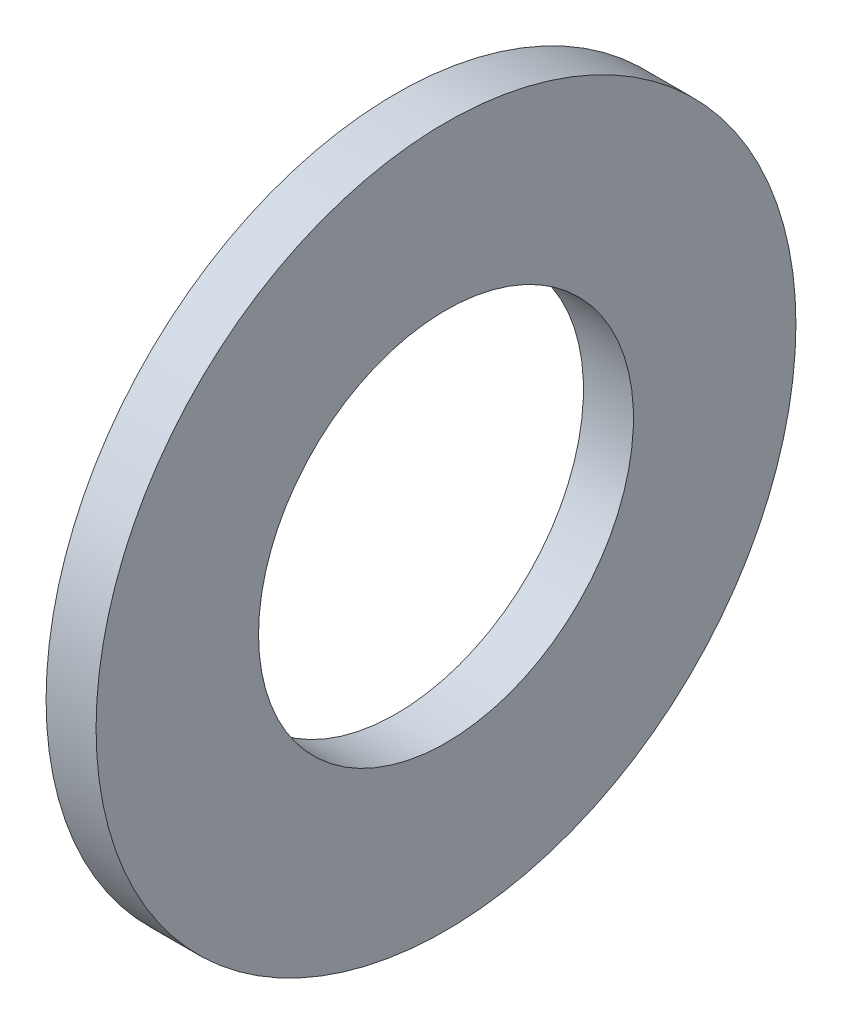
SolidWorks part; units mm, degrees
ref_plane "Front Plane" through (0, 0, 0) normal (0, 0, 1) x (1, 0, 0)
ref_plane "Top Plane" through (0, 0, 0) normal (0, 1, 0) x (1, 0, 0)
ref_plane "Right Plane" through (0, 0, 0) normal (1, 0, 0) x (0, 0, -1)
sketch "Sketch2" plane through (0, 0, 0) normal (0, 0, 1) x (1, 0, 0)
  line L0 (0, 0) -> (58.591, 0) construction
  line L2 (0, 0) -> (18.4, 0)
  line L3 (0, 0) -> (0, 2.5)
  line L4 (0, 2.5) -> (18.4, 2.5)
  line L5 (18.4, 0) -> (18.4, 2.5)
  line L6 (6, 2.5) -> (6, 6)
  line L11 (6, 6) -> (9.97, 6)
  line L16 (12.97, 6) -> (12.97, 3)
  line L17 (12.97, 3) -> (13.6304, 3)
  line L18 (13.6304, 3) -> (13.6304, 2.5)
  line L19 (13.6304, 2.5) -> (6, 2.5)
  line L22 (13.6304, 2.5) -> (16.1104, 2.5)
  line L23 (13.6304, 2.5) -> (13.6304, 4)
  line L24 (13.6304, 4) -> (16.1104, 4)
  line L25 (16.1104, 2.5) -> (16.1104, 4)
  line L27 (6, 6) -> (9.97, 6)
  line L28 (6, 6) -> (6, 9)
  line L29 (6, 9) -> (9.97, 9)
  line L30 (9.97, 6) -> (9.97, 9)
  line L31 (6, 9) -> (6, 8.25)
  line L32 (6, 8.25) -> (5, 8.25)
  line L33 (8.58, 22.001) -> (8.58, 12.476) construction
  line L34 (5, 12.476) -> (12.16, 12.476)
  line L35 (9.97, 9) -> (12.16, 9)
  line L36 (5, 7.5) -> (3, 7.5)
  line L37 (5, 8.25) -> (5, 12.476)
  line L38 (5, 7.5) -> (5, 14)
  line L39 (5, 14) -> (3, 14)
  line L40 (3, 7.5) -> (3, 14)
  line L41 (5, 22.001) -> (12.16, 22.001)
  line L42 (5, 22.001) -> (5, 30.1625)
  line L43 (5, 30.1625) -> (12.16, 30.1625)
  line L44 (12.16, 22.001) -> (12.16, 30.1625)
  line L49 (16.6304, 22.001) -> (16.6304, 7.5)
  line L51 (23.0104, 7.5) -> (23.0104, 6.5)
  line L54 (16.1104, 4) -> (13.6304, 4)
  line L56 (18.0304, 7.5) -> (23.0104, 7.5)
  line L57 (13.16, 22.001) -> (16.6304, 22.001)
  line L58 (16.1104, 3.5) -> (20.0104, 3.5)
  line L59 (29.9004, 14) -> (26.9004, 11)
  line L60 (4, 31.75) -> (18.0304, 31.75)
  line L61 (18.0304, 7.5) -> (23.0104, 7.5)
  line L62 (18.0304, 7.5) -> (18.0304, 12)
  line L63 (18.0304, 12) -> (23.0104, 12)
  line L64 (23.0104, 7.5) -> (23.0104, 12)
  line L65 (18.0304, 31.75) -> (18.0304, 12)
  line L66 (23.0104, 11) -> (26.9004, 11)
  line L67 (34.8004, 23) -> (31.3004, 19.5)
  line L68 (35.8004, 31) -> (38.7904, 33.99)
  line L69 (29.9004, 14) -> (29.9004, 15)
  line L70 (29.9004, 15) -> (22.9304, 15)
  line L71 (22.9304, 15) -> (21.0304, 15)
  line L72 (18.0304, 7.5) -> (16.6304, 7.5)
  line L73 (21.0304, 15) -> (21.0304, 43)
  line L74 (20.0304, 40) -> (10.0704, 40)
  line L75 (10.0704, 40) -> (4, 40)
  line L76 (21.0304, 43) -> (20.0304, 43)
  line L77 (22.9304, 15) -> (29.9004, 15)
  line L78 (22.9304, 15) -> (22.9304, 21)
  line L79 (22.9304, 21) -> (29.9004, 21)
  line L80 (29.9004, 15) -> (29.9004, 21)
  line L81 (10.0704, 40) -> (20.0304, 40)
  line L82 (10.0704, 40) -> (10.0704, 50)
  line L83 (10.0704, 50) -> (20.0304, 50)
  line L84 (20.0304, 40) -> (20.0304, 50)
  line L85 (4, 40) -> (4, 31.75)
  line L86 (12.97, 3) -> (12.97, 2.5)
  line L87 (31.3004, 19.5) -> (29.9004, 19.5)
  line L88 (21.51, 63.5) -> (21.51, 44)
  line L89 (21.51, 63.5) -> (25.9304, 63.5)
  line L90 (25.9304, 63.5) -> (25.9304, 25)
  line L91 (27.8304, 25) -> (25.9304, 25)
  line L92 (10.0704, 48) -> (9, 48)
  line L93 (9, 48) -> (9, 53.476)
  line L94 (9, 53.476) -> (20.0304, 53.476)
  line L95 (20.0304, 53.476) -> (20.0304, 50)
  line L96 (14.5152, 63.001) -> (14.5152, 53.476) construction
  line L97 (9, 63.001) -> (20.0304, 63.001)
  line L98 (9, 63.001) -> (9, 68.2625)
  line L99 (9, 68.2625) -> (20.0304, 68.2625)
  line L100 (20.0304, 63.001) -> (20.0304, 68.2625)
  line L101 (12.97, 6) -> (11.97, 6)
  line L102 (9, 42.5) -> (5, 42.5)
  line L103 (9, 42.5) -> (9, 55)
  line L104 (9, 55) -> (5, 55)
  line L105 (5, 42.5) -> (5, 55)
  line L106 (9.97, 6) -> (10.87, 6)
  line L107 (27.8304, 25) -> (34.8004, 25)
  line L108 (34.8004, 25) -> (34.8004, 23)
  line L109 (0, 0) -> (-2, 0)
  line L110 (0, 0) -> (0, 11)
  line L111 (27.8304, 25) -> (34.8004, 25)
  line L112 (27.8304, 25) -> (27.8304, 32.5)
  line L113 (27.8304, 32.5) -> (34.8004, 32.5)
  line L114 (34.8004, 25) -> (34.8004, 32.5)
  line L115 (35.8004, 31) -> (34.8004, 31)
  line L116 (27.8304, 32.5) -> (27.8304, 64.5)
  line L117 (21.1827, 74.025) -> (6.8477, 74.025)
  line L118 (6.8477, 74.025) -> (6.8477, 76.2)
  line L119 (38.7904, 47.29) -> (30.8304, 55.25)
  line L120 (0, 11) -> (-2, 11)
  line L121 (38.7904, 43.815) -> (30.8529, 43.815)
  line L123 (-4.8, 69.85) -> (1.55, 76.2)
  line L124 (38.7904, 47.29) -> (38.7904, 33.99)
  line L125 (-2, 0) -> (-2, 11)
  line L126 (38.7904, 37.465) -> (30.8529, 37.465)
  line L127 (30.8529, 43.815) -> (30.8529, 37.465)
  line L128 (6, 2.5) -> (6, 0)
  line L129 (0, 63.5) -> (0, 30)
  line L132 (5, 63.5) -> (0, 63.5)
  line L136 (-1.8, 30) -> (-11.76, 30)
  line L138 (-13.76, 25.4) -> (-2, 25.4)
  line L139 (-2, 25.4) -> (-2, 11.5)
  line L140 (27.8304, 64.5) -> (21.1827, 64.5)
  line L141 (-1.8, 30) -> (-11.76, 30)
  line L142 (-1.8, 30) -> (-1.8, 39)
  line L143 (-1.8, 39) -> (-11.76, 39)
  line L144 (-11.76, 30) -> (-11.76, 39)
  line L145 (21.1827, 64.5) -> (21.1827, 74.025)
  line L146 (-12.76, 37) -> (-12.76, 47.29)
  line L147 (-12.76, 37) -> (-11.76, 37)
  line L148 (30.8304, 55.25) -> (30.8304, 76.2)
  line L149 (11.97, 6) -> (11.97, 5.45)
  line L154 (-2, 11.5) -> (1, 11.5)
  line L155 (5, 60.6197) -> (24.05, 60.6197)
  line L160 (5, 60.6197) -> (5, 55.8572)
  line L161 (5, 55.8572) -> (24.05, 55.8572)
  line L166 (24.05, 60.6197) -> (24.05, 55.8572)
  line L167 (5, 60.6197) -> (24.05, 55.8572) construction
  line L172 (5, 55.8572) -> (24.05, 60.6197) construction
  line L173 (24.05, 62.2072) -> (25.9304, 62.2072)
  line L174 (11.97, 5.45) -> (10.87, 5.45)
  line L175 (10.87, 6) -> (10.87, 5.45)
  line L176 (24.05, 62.2072) -> (24.05, 54.2697)
  line L177 (24.05, 54.2697) -> (25.9304, 54.2697)
  line L178 (25.9304, 62.2072) -> (25.9304, 54.2697)
  line L179 (24.05, 62.2072) -> (25.9304, 54.2697) construction
  line L180 (24.05, 54.2697) -> (25.9304, 62.2072) construction
  line L181 (3, 19.6197) -> (15.7, 19.6197)
  line L182 (3, 19.6197) -> (3, 14.8572)
  line L183 (3, 14.8572) -> (15.7, 14.8572)
  line L184 (15.7, 19.6197) -> (15.7, 14.8572)
  line L185 (3, 19.6197) -> (15.7, 14.8572) construction
  line L186 (3, 14.8572) -> (15.7, 19.6197) construction
  line L187 (15.7, 21.2072) -> (16.6304, 21.2072)
  line L188 (15.7, 21.2072) -> (15.7, 13.2697)
  line L189 (15.7, 13.2697) -> (16.6304, 13.2697)
  line L190 (16.6304, 21.2072) -> (16.6304, 13.2697)
  line L191 (15.7, 21.2072) -> (16.6304, 13.2697) construction
  line L192 (15.7, 13.2697) -> (16.6304, 21.2072) construction
  line L193 (1, 11.5) -> (1, 6.5)
  line L194 (1, 6.5) -> (3, 6.5)
  line L195 (23.0104, 6.5) -> (20.0104, 3.5)
  line L196 (5, 63.5) -> (5, 42.5)
  line L197 (5, 42.5) -> (3, 42.5)
  line L198 (3, 42.5) -> (3, 6.5)
  line L199 (6, 0) -> (12.97, 0)
  line L200 (12.97, 0) -> (12.97, 2.5)
  line L201 (18.0304, 31.75) -> (18.0304, 35.875)
  line L202 (18.0304, 35.875) -> (21.0304, 35.875)
  line L203 (30.8304, 76.2) -> (6.8477, 76.2)
  line L204 (3.4027, 69.85) -> (7.8477, 69.85) construction
  line L205 (7.8477, 67.4687) -> (26.8977, 67.4688)
  line L206 (7.8477, 74.025) -> (7.8477, 64.5)
  line L207 (7.8477, 64.5) -> (-1.8, 64.5)
  line L208 (-1.8, 64.5) -> (-1.8, 39)
  line L209 (-12.76, 47.29) -> (-4.8, 55.25)
  line L210 (-4.8, 55.25) -> (-4.8, 69.85)
  line L211 (7.8477, 67.4687) -> (7.8477, 72.2313)
  line L212 (7.8477, 72.2313) -> (26.8977, 72.2313)
  line L213 (26.8977, 67.4688) -> (26.8977, 72.2313)
  line L214 (26.8977, 73.8187) -> (30.8304, 73.8187)
  line L215 (26.8977, 73.8187) -> (26.8977, 65.8813)
  line L216 (26.8977, 65.8813) -> (30.8304, 65.8813)
  line L217 (30.8304, 73.8187) -> (30.8304, 65.8813)
  line L218 (3.4027, 72.2313) -> (25.6277, 72.2313)
  line L219 (3.4027, 72.2313) -> (3.4027, 67.4687)
  line L220 (3.4027, 67.4687) -> (25.6277, 67.4687)
  line L221 (25.6277, 72.2313) -> (25.6277, 67.4687)
  line L222 (25.6277, 69.85) -> (21.1827, 69.85) construction
  line L223 (21.51, 44) -> (22.9304, 44)
  line L224 (22.9304, 44) -> (22.9304, 21)
  line L225 (13.6304, 4) -> (13.6304, 12.2697)
  line L226 (13.6304, 12.2697) -> (13.16, 12.2697)
  line L227 (13.16, 12.2697) -> (13.16, 22.001)
  line L228 (12.16, 9) -> (12.16, 12.476)
  line L229 (-1.8, 30) -> (0, 30)
  line L230 (9, 65.6317) -> (3.4027, 65.6317) construction
  line L231 (20.0304, 65.6317) -> (25.6277, 65.6317) construction
  line L232 (1.55, 76.2) -> (6.8477, 76.2)
  line L233 (-11.76, 30) -> (-13.76, 30)
  line L234 (-13.76, 30) -> (-13.76, 25.4)
  circle A0 centre (26.8804, 25.95) radius 0.95
  circle A1 centre (21.9804, 15.95) radius 0.95
  circle A2 centre (17.3304, 8.2) radius 0.7
  circle A3 centre (10.42, 6.45) radius 0.45
  circle A4 centre (-0.9, 30.9) radius 0.9
  point P7 (24.9902, 58.2385)
  point P131 (16.1652, 17.2385)
  point P135 (14.525, 58.2385)
  point P146 (9.35, 17.2385)
sketch "Sketch3" plane through (0, 0, 0) normal (0, 0, 1) x (1, 0, 0)
  line L0 (5, 7.5) -> (5, 14) construction
  line L1 (5, 14) -> (3, 14) construction
  line L2 (3, 7.5) -> (3, 14) construction
  line L3 (5, 7.5) -> (3, 7.5) construction
  line L4 (5, 7.5) -> (5, 14)
  line L5 (5, 14) -> (3, 14)
  line L6 (3, 7.5) -> (3, 14)
  line L7 (5, 7.5) -> (3, 7.5)
revolve "Revolve1" add sketch "Sketch3" angle 360 about L0
